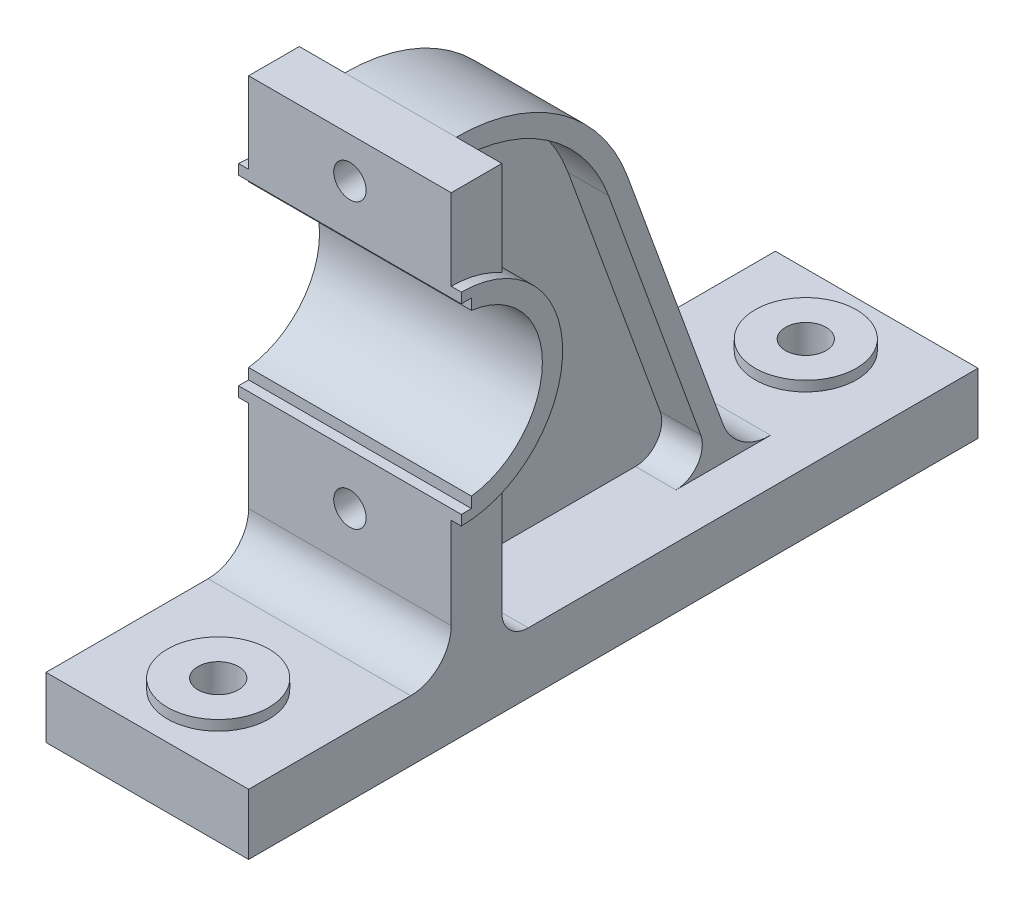
SolidWorks part; units mm, degrees
ref_plane "Front Plane" through (0, 0, 0) normal (0, 0, 1) x (1, 0, 0)
ref_plane "Top Plane" through (0, 0, 0) normal (0, 1, 0) x (1, 0, 0)
ref_plane "Right Plane" through (0, 0, 0) normal (1, 0, 0) x (0, 0, -1)
sketch "Sketch1" plane through (0, 0, 0) normal (1, 0, 0) x (0, 0, -1)
  line L0 (0, 0) -> (0, 30)
  line L1 (0, 30) -> (100, 30)
  line L2 (100, 30) -> (100, 235)
  line L3 (100, 235) -> (125, 235)
  line L4 (125, 235) -> (125, 30)
  line L5 (125, 30) -> (360, 30)
  line L6 (360, 30) -> (360, 0)
  line L7 (360, 0) -> (0, 0)
  dimension "D1" = 360
  dimension "D2" = 30
  dimension "D3" = 25
  dimension "D4" = 100
  dimension "D5" = 235
extrude "Boss-Extrude1" add sketch "Sketch1" along normal mid plane 100
sketch "Sketch2" plane through (0, 0, 0) normal (1, 0, 0) x (0, 0, -1)
  line L0 (100, 235) -> (100, 30) construction
  line L1 (0, 0) -> (360, 0) construction
  line L2 (100, 195) -> (100, 95)
  arc A0 (100, 195) -> (100, 95) centre (100, 145) cw
  dimension "D1" = 50
  dimension "D2" = 145
extrude "Boss-Extrude2" add sketch "Sketch2" along normal mid plane 110
sketch "Sketch3" plane through (0, 0, 0) normal (1, 0, 0) x (0, 0, -1)
  line L0 (125, 235) -> (125, 30)
  line L1 (262.6326, 30) -> (209.5723, 175.7818)
  line L2 (125, 30) -> (262.6326, 30)
  line L3 (0, 0) -> (360, 0) construction
  line L4 (360, 30) -> (125, 30) construction
  arc A0 (125, 235) -> (209.5723, 175.7818) centre (125, 145) cw
  dimension "D1" = 90
  dimension "D2" = 145
  dimension "D3" = 110
extrude "Boss-Extrude3" add sketch "Sketch3" along normal mid plane 55
sketch "Sketch4" plane through (27.5, 0, 0) normal (1, 0, 0) x (0, 0, -1)
  line L1 (125, 225) -> (125, 188.3013)
  line L2 (253.2357, 26.5798) -> (200.1754, 172.3616)
  line L3 (251.9908, 30) -> (200.1754, 172.3616)
  line L5 (125, 101.6987) -> (125, 30)
  line L6 (125, 30) -> (251.9908, 30)
  line L7 (125, 30) -> (262.6326, 30) construction
  arc A3 (200.1754, 172.3616) -> (125, 225) centre (125, 145) ccw
  arc A4 (200.1754, 172.3616) -> (125, 225) centre (125, 145) ccw
  arc A5 (125, 101.6987) -> (125, 188.3013) centre (100, 145) ccw construction
  arc A6 (125, 101.6987) -> (125, 188.3013) centre (100, 145) ccw
  dimension "D1" = 10
extrude "Cut-Extrude1" cut sketch "Sketch4" against normal blind 20
mirror "Mirror1" about plane through (0, 0, 0) normal (1, 0, 0) of "Cut-Extrude1"
sketch "Sketch5" plane through (0, 0, 0) normal (1, 0, 0) x (0, 0, -1)
  line L0 (100, 195) -> (100, 95) construction
  line L1 (100, 185) -> (100, 105)
  arc A0 (100, 105) -> (100, 185) centre (100, 145) ccw
  dimension "D1" = 40
extrude "Cut-Extrude2" cut sketch "Sketch5" against normal through all both and the other way through all
sketch "Sketch6" plane through (55, 0, 0) normal (1, 0, 0) x (0, 0, -1)
  line L1 (105, 100) -> (95, 100)
  line L2 (105, 100) -> (105, 190)
  line L3 (105, 190) -> (95, 190)
  line L4 (95, 100) -> (95, 190)
  line L5 (105, 100) -> (95, 190) construction
  line L6 (105, 190) -> (95, 100) construction
  point P0 (100, 145)
  point P6 (100, 190)
  dimension "D1" = 5
  dimension "D2" = 5
extrude "Cut-Extrude3" cut sketch "Sketch6" against normal through all both and the other way through all
sketch "Sketch7" plane through (0, 30, 0) normal (0, 1, 0) x (1, 0, 0)
  circle A0 centre (0, 35) radius 25
  dimension "D1" = 50
  dimension "D2" = 35
extrude "Boss-Extrude4" add sketch "Sketch7" along normal blind 5
pattern_linear "LPattern1" count 2 spacing 290 along (0, 0, -1) of "Boss-Extrude4"
hole_wizard "Hole1" positions "Sketch8" profile "Sketch9" legacy end condition through all
sketch "Sketch8" plane through (0, 35, 0) normal (0, 1, 0) x (1, 0, 0)
  point P0 (0, 35)
  point P3 (0, 325)
sketch "Sketch9" plane through (0, 35, -35) normal (1, 0, 0) x (0, 0, 1)
  line L0 (0, 0) -> (0, 35)
  line L1 (0, 35) -> (10, 35)
  line L2 (10, 35) -> (10, 0)
  line L3 (10, 0) -> (0, 0)
  line L4 (0, 110) -> (0, -10) construction
  dimension "Diameter" = 20
  dimension "Depth" = 35
hole_wizard "Hole2" positions "Sketch10" profile "Sketch11" legacy
sketch "Sketch10" plane through (0, 0, -100) normal (0, 0, 1) x (1, 0, 0)
  point P3 (0, 215)
  dimension "D1" = 215
sketch "Sketch11" plane through (0, 215, -100) normal (1, 0, 0) x (0, -1, 0)
  line L0 (0, 0) -> (0, 25)
  line L1 (0, 25) -> (8, 25)
  line L2 (8, 25) -> (8, 0)
  line L3 (8, 0) -> (0, 0)
  line L4 (0, 110) -> (0, -10) construction
  dimension "Diameter" = 16
  dimension "Depth" = 25
pattern_linear "LPattern2" count 2 spacing 140 along (0, -1, 0) of "Hole2"
fillet "Fillet1" radius 25 1 edges at (0, 30, -262.6326)
fillet "Fillet2" radius 13 4 edges at (-28.75, 30, -125) (28.75, 30, -125) (-17.5, 30, -251.9908) (17.5, 30, -251.9908)
fillet "Fillet3" radius 20 1 edges at (0, 30, -100)
fillet "Fillet4" radius 10 2 edges at (-17.5, 225, -125) (17.5, 225, -125)
